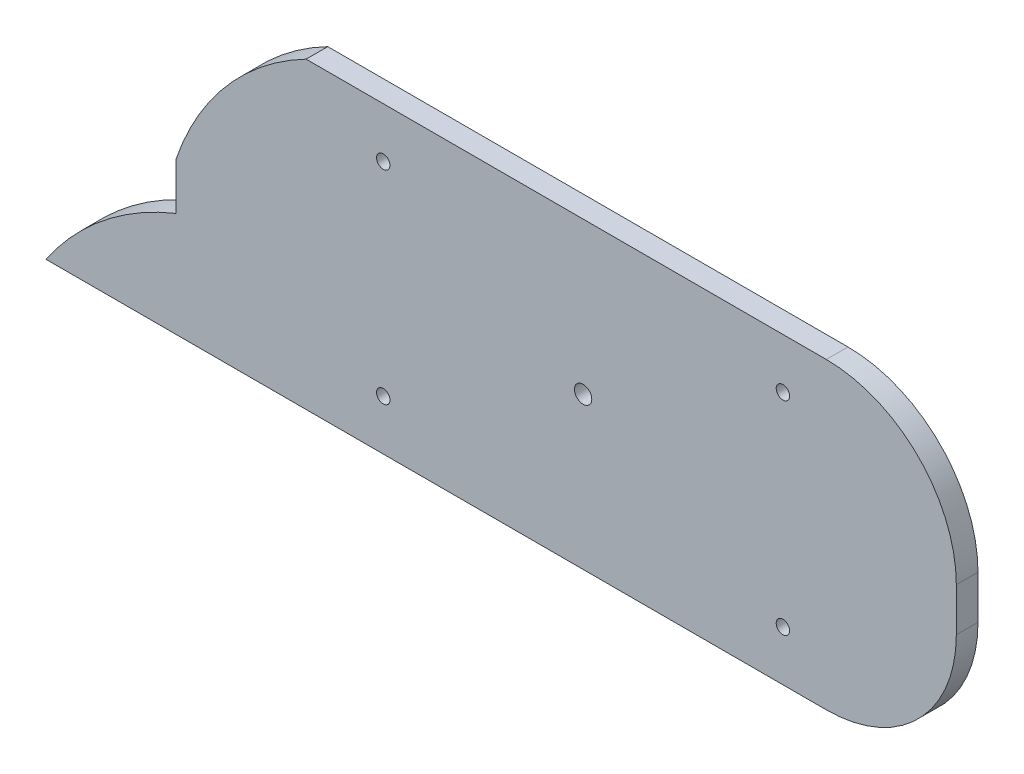
SolidWorks part; units mm, degrees
material "1060 Alloy"
ref_plane "Front Plane" through (0, 0, 0) normal (0, 0, 1) x (1, 0, 0)
ref_plane "Top Plane" through (0, 0, 0) normal (0, 1, 0) x (1, 0, 0)
ref_plane "Right Plane" through (0, 0, 0) normal (1, 0, 0) x (0, 0, -1)
sketch "Sketch2" plane through (0, 0, 0) normal (0, 0, 1) x (1, 0, 0)
  line L0 (0, 0) -> (457.2, 0)
  line L1 (76.2, 0) -> (76.2, 88.9) construction
  line L2 (152.4, 0) -> (152.4, 177.8) construction
  line L9 (457.2, 177.8) -> (152.4, 177.8)
  line L14 (533.4, 76.2) -> (533.4, 101.6)
  line L16 (76.2, 88.9) -> (76.2, 61.4013)
  arc A5 (0, 0) -> (76.2, 61.4013) centre (138.3869, -93.7571) cw
  arc A6 (457.2, 0) -> (533.4, 76.2) centre (457.2, 76.2) ccw
  arc A7 (533.4, 101.6) -> (457.2, 177.8) centre (457.2, 101.6) ccw
  arc A8 (76.2, 88.9) -> (152.4, 177.8) centre (224.2925, 39.0707) cw
  dimension "D6" = 167.1566
  dimension "D7" = 88.9
  dimension "D5" = 177.8
  dimension "D1" = 76.2
  dimension "D4" = 457.2
  dimension "D9" = 138.3869
  dimension "D8" = 156.2509
  dimension "D2" = 76.2
  dimension "D3" = 152.4
extrude "Boss-Extrude1" add sketch "Sketch2" along normal blind 12.7
sketch "Sketch4" plane through (0, 0, 12.7) normal (0, 0, 1) x (1, 0, 0)
  line L0 (314.706, 0) -> (314.706, 177.8) construction
  line L1 (0, 0) -> (457.2, 0) construction
  line L2 (457.2, 177.8) -> (152.4, 177.8) construction
  line L3 (76.2, 88.9) -> (533.4, 88.9) construction
  line L4 (76.2, 88.9) -> (76.2, 61.4013) construction
  line L6 (533.4, 76.2) -> (533.4, 101.6) construction
  circle A0 centre (314.706, 88.9) radius 5.08
  circle A3 centre (431.8, 148.4376) radius 3.937
  circle A5 centre (197.612, 148.4376) radius 3.937
  circle A6 centre (197.612, 29.3624) radius 3.937
  circle A7 centre (431.8, 29.3624) radius 3.937
  dimension "D1" = 10.16
  dimension "D4" = 7.874
  dimension "D5" = 29.3624
  dimension "D6" = 117.094
  dimension "D2" = 314.706
  dimension "D3" = 88.9
extrude "Cut-Extrude2" cut sketch "Sketch4" against normal through all
equation "\"0.5n\"=0.25"
equation "\".5n\"=0.25"
